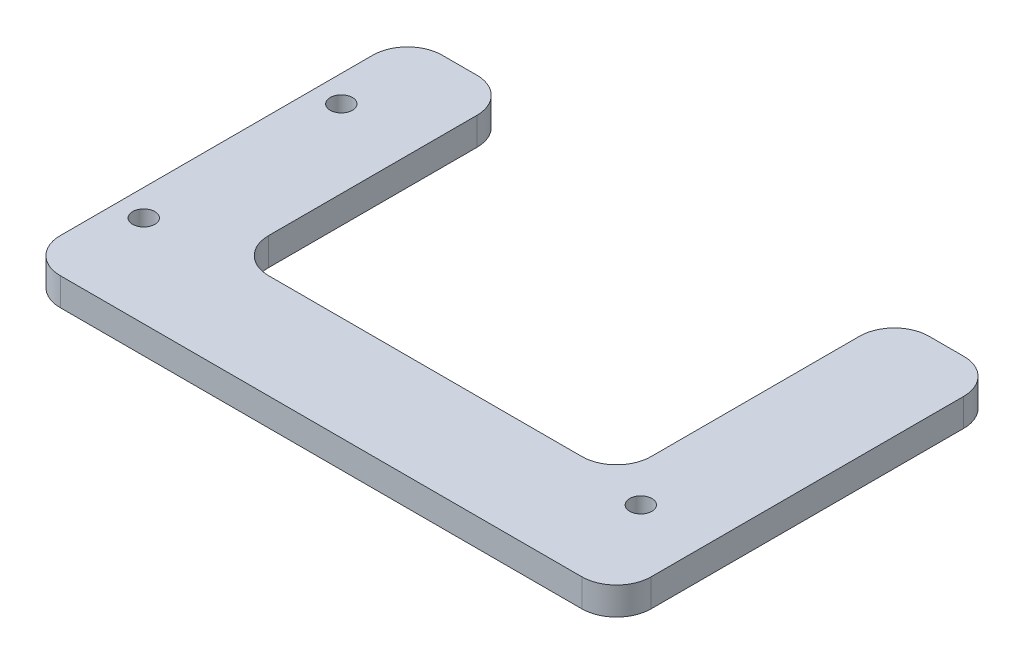
SolidWorks part; units mm, degrees
ref_plane "前视基准面" through (0, 0, 0) normal (0, 0, 1) x (1, 0, 0)
ref_plane "上视基准面" through (0, 0, 0) normal (0, 1, 0) x (1, 0, 0)
ref_plane "右视基准面" through (0, 0, 0) normal (1, 0, 0) x (0, 0, -1)
sketch "草图1" plane through (0, 0, 0) normal (0, 1, 0) x (1, 0, 0)
  line L0 (-38.74, 14.16) -> (-38.74, -14.29) construction
  line L1 (42.55, -27.5) -> (-42.55, -27.5)
  line L2 (42.55, -27.5) -> (42.55, 27.5)
  line L3 (42.55, 27.5) -> (-42.55, 27.5)
  line L4 (-42.55, -27.5) -> (-42.55, 27.5)
  line L5 (42.55, -27.5) -> (-42.55, 27.5) construction
  line L6 (42.55, 27.5) -> (-42.55, -27.5) construction
  line L7 (-38.74, -14.29) -> (32.84, -14.29) construction
  circle A0 centre (-38.74, 14.16) radius 1.6
  circle A1 centre (-38.74, -14.29) radius 1.6
  circle A2 centre (32.84, -14.29) radius 1.6
  point P0 (0, 0)
  dimension "D5" = 3.2
  dimension "D1" = 55
  dimension "D2" = 85.1
  dimension "D3" = 3.81
  dimension "D4" = 9.71
  dimension "D6" = 13.21
  dimension "D7" = 13.34
extrude "凸台-拉伸1" add sketch "草图1" along normal blind 4
sketch "草图2" plane through (0, 0, 0) normal (0, 1, 0) x (1, 0, 0)
  line L0 (-16, 7.5) -> (16, 7.5) construction
  line L1 (0, 7.5) -> (0, 0) construction
  line L2 (42.55, 27.5) -> (-42.55, 27.5) construction
  line L3 (-16, 7.5) -> (-16, -2.5) construction
  line L4 (-16, -2.5) -> (16, -2.5) construction
  line L5 (16, -2.5) -> (16, 7.5) construction
  circle A0 centre (-16, 7.5) radius 3
  circle A1 centre (16, 7.5) radius 3
  circle A2 centre (-16, -2.5) radius 3
  circle A3 centre (16, -2.5) radius 3
  dimension "D2" = 6
  dimension "D1" = 20
  dimension "D3" = 32
  dimension "D4" = 10
sketch "草图3" plane through (0, 0, 0) normal (0, 1, 0) x (1, 0, 0)
  line L0 (42.55, 27.5) -> (-42.55, 27.5) construction
  line L1 (27.55, -12.5) -> (-27.55, -12.5)
  line L2 (27.55, -12.5) -> (27.55, 27.5)
  line L3 (27.55, 27.5) -> (-27.55, 27.5)
  line L4 (-27.55, -12.5) -> (-27.55, 27.5)
  line L5 (27.55, -12.5) -> (-27.55, 27.5) construction
  line L6 (27.55, 27.5) -> (-27.55, -12.5) construction
  line L7 (0, 7.5) -> (0, 0) construction
  line L8 (42.55, -27.5) -> (42.55, 27.5) construction
  line L9 (-42.55, -27.5) -> (42.55, -27.5) construction
  point P0 (0, 7.5)
  dimension "D1" = 15
  dimension "D2" = 15
extrude "切除-拉伸2" cut sketch "草图3" along normal up to next
fillet "圆角1" radius 5 8 edges at (27.55, 2, 12.5) (27.55, 2, -27.5) (42.55, 2, -27.5) (42.55, 2, 27.5) (-42.55, 2, 27.5) (-27.55, 2, 12.5) (-42.55, 2, -27.5) (-27.55, 2, -27.5)
